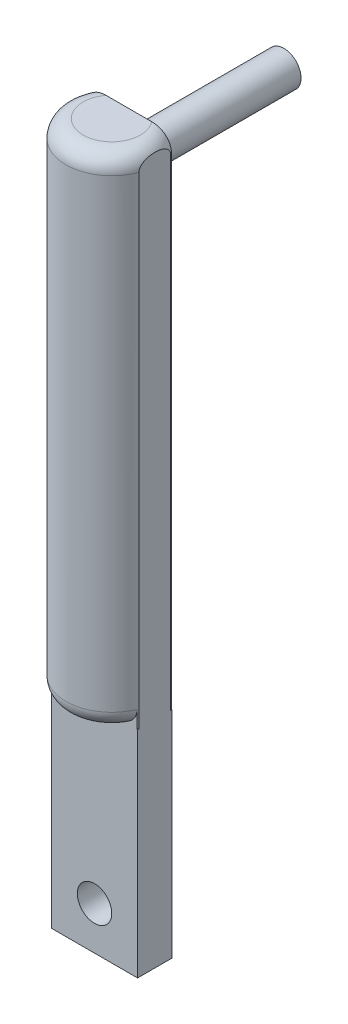
SolidWorks part; units mm, degrees
ref_plane "Plan de face" through (0, 0, 0) normal (0, 0, 1) x (1, 0, 0)
ref_plane "Plan de dessus" through (0, 0, 0) normal (0, 1, 0) x (1, 0, 0)
ref_plane "Plan de droite" through (0, 0, 0) normal (1, 0, 0) x (0, 0, -1)
sketch "Esquisse1" plane through (0, 0, 0) normal (0, 0, 1) x (1, 0, 0)
  line L0 (-25, -87.5) -> (25, -37.5) construction
  line L1 (-25, -87.5) -> (25, -87.5)
  line L2 (-25, -87.5) -> (-25, 37.5)
  line L3 (-25, 37.5) -> (25, 37.5)
  line L4 (25, -87.5) -> (25, 37.5)
  circle A1 centre (0, -62.5) radius 10
  dimension "D1" = 50
  dimension "D2" = 45
  dimension "D3" = 125
extrude "Boss.-Extru.1" add sketch "Esquisse1" along normal blind 20
sketch "Esquisse2" plane through (0, 37.5, 0) normal (0, 1, 0) x (1, 0, 0)
  line L0 (-25, -20) -> (25, 0) construction
  line L1 (25, 0) -> (-25, 0)
  circle A0 centre (0, -10) radius 26.634
  line M3 (-25, 0) -> (-25, -20)
  line M4 (-25, -20) -> (25, -20)
  line M5 (25, -20) -> (25, 0)
extrude "Boss.-Extru.2" add sketch "Esquisse2" along normal blind 290 contours A0 M4 | A0 L0 L1 M3 | L0 A0 M4 M5 region at (-8.3267, 37.5, 6.6657) region at (8.3267, 37.5, 13.3343) region at (0, 37.5, 26.8717)
sketch "Esquisse3" plane through (0, 327.5, 0) normal (0, 1, 0) x (1, 0, 0)
  line L0 (-24.6855, 0) -> (25, -19.1854) construction
sketch "Esquisse4" plane through (0, 0, 0) normal (0, 0, -1) x (-1, 0, 0)
  line L0 (24.6855, 327.5) -> (-24.6855, 278.1291) construction
  line L1 (-24.6855, 327.5) -> (-24.6855, 37.5) construction
  line L2 (24.6855, 327.5) -> (24.6855, 37.5) construction
  circle A0 centre (0, 302.8145) radius 10
  dimension "D2" = 20
  dimension "D1" = 45
extrude "Boss.-Extru.3" add sketch "Esquisse4" along normal blind 90
fillet "Congé1" radius 10 2 edges at (0, 37.5, 36.634) (0, 327.5, 36.634)
